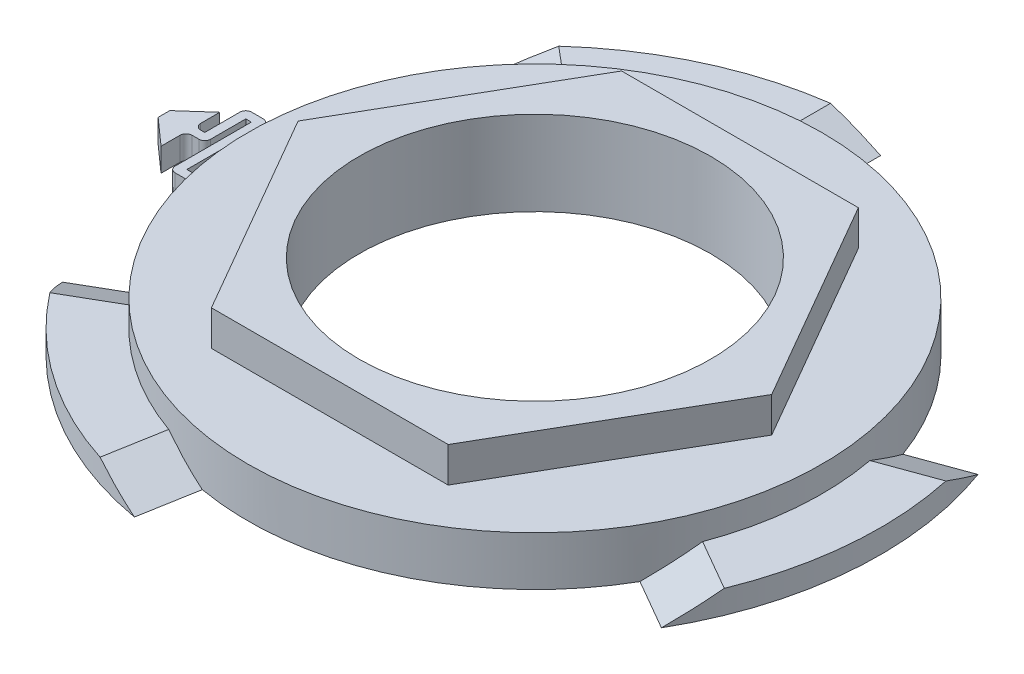
SolidWorks part; units mm, degrees
ref_plane "Ebene vorne" through (0, 0, 0) normal (0, 0, 1) x (1, 0, 0)
ref_plane "Ebene oben" through (0, 0, 0) normal (0, 1, 0) x (1, 0, 0)
ref_plane "Ebene rechts" through (0, 0, 0) normal (1, 0, 0) x (0, 0, -1)
sketch "Skizze1" plane through (0, 0, 0) normal (0, 1, 0) x (1, 0, 0)
  line L0 (0, 0) -> (0, 49) construction
  line L1 (0, 0) -> (-37.5362, 31.4966) construction
  line L2 (-37.5362, 31.4966) -> (-45.1966, 37.9245)
  line L3 (0, 49) -> (0, 59)
  line L4 (46.0449, 16.759) -> (55.4419, 20.1792)
  line L5 (42.4352, -24.5) -> (51.0955, -29.5)
  line L6 (-8.5088, -48.2556) -> (-10.2452, -58.1037)
  line L7 (-42.4352, -24.5) -> (-51.0955, -29.5)
  arc A0 (-51.0955, -29.5) -> (-10.2452, -58.1037) centre (0, 0) ccw
  arc A1 (-8.5088, -48.2556) -> (42.4352, -24.5) centre (0, 0) ccw
  arc A2 (0, 59) -> (-45.1966, 37.9245) centre (0, 0) ccw
  arc A3 (51.0955, -29.5) -> (55.4419, 20.1792) centre (0, 0) ccw
  arc A4 (46.0449, 16.759) -> (0, 49) centre (0, 0) ccw
  arc A5 (-37.5362, 31.4966) -> (-42.4352, -24.5) centre (0, 0) ccw
  point P18 (0, 0)
  dimension "D1" = 118
  dimension "D2" = 98
  dimension "D3" = 50
  dimension "D4" = 3
extrude "Aufsatz-Linear austragen1" add sketch "Skizze1" along normal blind 4
sketch "Skizze2" plane through (0, 4, 0) normal (0, 1, 0) x (1, 0, 0)
  circle A0 centre (0, 0) radius 49
extrude "Aufsatz-Linear austragen2" add sketch "Skizze2" along normal blind 4.4
chamfer "Fase1" distance 4 distance2 8 6 edges at (46.7654, 4, 27) (50.7434, 4, -18.4691) (0, 4, -54) (-41.3664, 4, -34.7105) (-9.377, 4, 53.1796) (-46.7654, 4, 27) first distance on face at (46.7654, 2, 27) first distance on face at (50.7434, 2, -18.4691) first distance on face at (0, 2, -54) first distance on face at (-41.3664, 2, -34.7105) first distance on face at (-9.377, 2, 53.1796) first distance on face at (-46.7654, 2, 27)
sketch "Skizze3" plane through (0, 8.4, 0) normal (0, 1, 0) x (1, 0, 0)
  line L0 (0, 0) -> (40.4145, 0) construction
  line L1 (40.4145, 0) -> (20.2073, 35)
  line L2 (20.2073, 35) -> (-20.2073, 35)
  line L3 (-20.2073, 35) -> (-40.4145, 0)
  line L4 (-40.4145, 0) -> (-20.2073, -35)
  line L5 (-20.2073, -35) -> (20.2073, -35)
  line L6 (20.2073, -35) -> (40.4145, 0)
  circle A0 centre (0, 0) radius 35 construction
  dimension "D1" = 70
extrude "Aufsatz-Linear austragen3" add sketch "Skizze3" along normal blind 6
sketch "Skizze4" plane through (0, 14.4, 0) normal (0, 1, 0) x (1, 0, 0)
  circle A0 centre (0, 0) radius 30
  dimension "D1" = 60
extrude "Schnitt-Linear austragen2" cut sketch "Skizze4" against normal through all
sketch "Skizze5" plane through (0, 0, 0) normal (0, -1, 0) x (1, 0, 0)
  line L0 (-49, 0) -> (-51.4475, 0) construction
  line L1 (-51.4475, 0) -> (-51.4475, 7) construction
  line L2 (-51.4475, 7) -> (-53.895, 7) construction
  line L3 (-53.895, 7) -> (-53.895, -7) construction
  line L4 (-53.895, -7) -> (-56.3425, -7) construction
  line L5 (-56.3425, -7) -> (-56.3425, 0) construction
  line L6 (-56.3425, 0) -> (-61.0453, 0) construction
  line L7 (-51.4475, 0) -> (-56.3425, 0) construction
  line L8 (-58.7878, -5) -> (-63.3028, -5)
  line L9 (-58.7878, -5) -> (-58.7878, -0.75)
  line L10 (-58.7878, 5) -> (-63.3028, 5)
  line L11 (-63.3028, -5) -> (-63.3028, 5)
  line L12 (-58.7878, -5) -> (-63.3028, 5) construction
  line L13 (-58.7878, 5) -> (-63.3028, -5) construction
  line L14 (-48.9943, 0.75) -> (-50.6975, 0.75)
  line L15 (-50.6975, 0.75) -> (-50.6975, 7.75)
  line L16 (-50.6975, 7.75) -> (-54.645, 7.75)
  line L17 (-54.645, 7.75) -> (-54.645, -6.25)
  line L18 (-54.645, -6.25) -> (-55.5925, -6.25)
  line L19 (-55.5925, -6.25) -> (-55.5925, 0.75)
  line L20 (-55.5925, 0.75) -> (-58.7878, 0.75)
  line L21 (-48.9943, -0.75) -> (-52.1975, -0.75)
  line L22 (-52.1975, -0.75) -> (-52.1975, 6.25)
  line L23 (-52.1975, 6.25) -> (-53.145, 6.25)
  line L24 (-53.145, 6.25) -> (-53.145, -7.75)
  line L25 (-53.145, -7.75) -> (-57.0925, -7.75)
  line L26 (-57.0925, -7.75) -> (-57.0925, -0.75)
  line L27 (-57.0925, -0.75) -> (-58.7878, -0.75)
  line L28 (-58.7878, 0.75) -> (-58.7878, 5)
  line L29 (-49, -0.75) -> (-52.1975, -0.75) construction
  line L30 (-57.0925, -0.75) -> (-61.0453, -0.75) construction
  line L31 (-55.5925, 0.75) -> (-61.0453, 0.75) construction
  line L32 (-49, 0.75) -> (-50.6975, 0.75) construction
  arc A0 (-48.9943, 0.75) -> (-48.9943, -0.75) centre (0, 0) ccw
  circle A1 centre (0, 0) radius 63.5 construction
  circle A2 centre (0, 0) radius 59 construction
  point P17 (-63.5, 0)
  point P18 (-63.5, 0)
  point P35 (-49.7216, -1)
  point P37 (-49.5763, 1)
  dimension "D1" = 98
  dimension "D2" = 127
  dimension "D3" = 118
  dimension "D4" = 10
  dimension "D5" = 2.4475
  dimension "D6" = 2.4475
  dimension "D7" = 2.4475
  dimension "D8" = 7
  dimension "D9" = 14
  dimension "D10" = 0.75
  dimension "D11" = 0.75
extrude "Aufsatz-Linear austragen4" add sketch "Skizze5" against normal up to surface (4 mm away) up to face at (-30.3355, 4, 43.3236)
fillet "Verrundung2" radius 1 10 edges at (-48.9943, 2, 0.75) (-48.9943, 2, -0.75) (-58.7878, 2, -0.75) (-58.7878, 2, 0.75) (-55.5925, 2, 0.75) (-50.6975, 2, 7.75) (-54.645, 2, 7.75) (-57.0925, 2, -7.75) (-53.145, 2, -7.75) (-52.1975, 2, -0.75)
chamfer "Fase2" distance 4 distance2 4.5 1 edges at (-63.3028, 2, 5) first distance on face at (-63.3028, 2, 0)
chamfer "Fase3" distance 4.5 distance2 4 1 edges at (-63.3028, 2, -5) first distance on face at (-61.0453, 2, -5)
